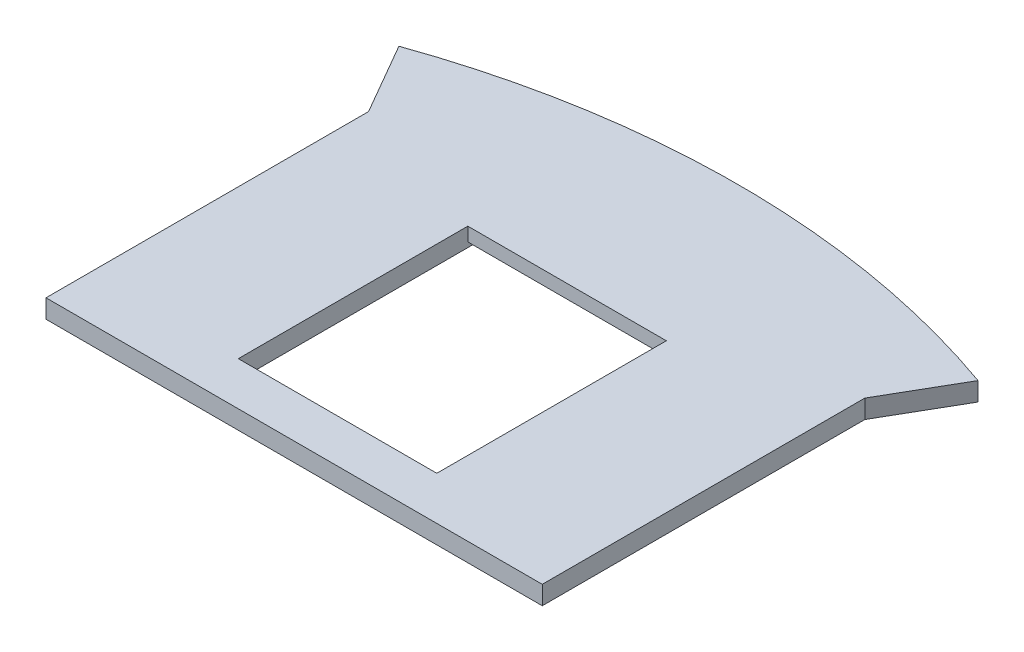
SolidWorks part; units mm, degrees
ref_plane "Front Plane" through (0, 0, 0) normal (0, 0, 1) x (1, 0, 0)
ref_plane "Top Plane" through (0, 0, 0) normal (0, 1, 0) x (1, 0, 0)
ref_plane "Right Plane" through (0, 0, 0) normal (1, 0, 0) x (0, 0, -1)
sketch "Sketch1" plane through (0, 0, 0) normal (0, 1, 0) x (1, 0, 0)
  line L0 (-40, 68) -> (-40, 120)
  line L1 (-40, 120) -> (-46.6772, 131.5652)
  line L2 (46.6772, 131.5652) -> (40, 120)
  line L3 (40, 120) -> (40, 68)
  line L4 (40, 68) -> (-40, 68)
  arc A0 (-46.6772, 131.5652) -> (46.6772, 131.5652) centre (0, 0) cw
  dimension "D1" = 139.6
  dimension "D2" = 150
  dimension "D3" = 40
  dimension "D4" = 80
  dimension "D5" = 150
  dimension "D6" = 52
  dimension "D7" = 68
extrude "Boss-Extrude1" add sketch "Sketch1" along normal blind 3
sketch "Sketch2" plane through (0, 3, 0) normal (0, 1, 0) x (1, 0, 0)
  line L1 (-16, 112) -> (16, 112)
  line L2 (-16, 112) -> (-16, 75)
  line L3 (-16, 75) -> (16, 75)
  line L4 (16, 112) -> (16, 75)
  dimension "D1" = 32
  dimension "D2" = 37
  dimension "D3" = 75
  dimension "D4" = 16
extrude "Cut-Extrude1" cut sketch "Sketch2" against normal up to next
sketch "Sketch3" plane through (0, 0, 0) normal (0, -1, 0) x (1, 0, 0)
  line L0 (16, -75) -> (16, -112) construction
  line L1 (-16, -71.5) -> (16, -71.5)
  line L2 (-16, -71.5) -> (-16, -115.5)
  line L3 (-16, -115.5) -> (16, -115.5)
  line L4 (16, -71.5) -> (16, -115.5)
  line L5 (-16, -112) -> (-16, -75) construction
  line L6 (16, -112) -> (-16, -112) construction
  dimension "D1" = 44
  dimension "D2" = 3.5
extrude "Cut-Extrude2" cut sketch "Sketch3" against normal blind 0.8
